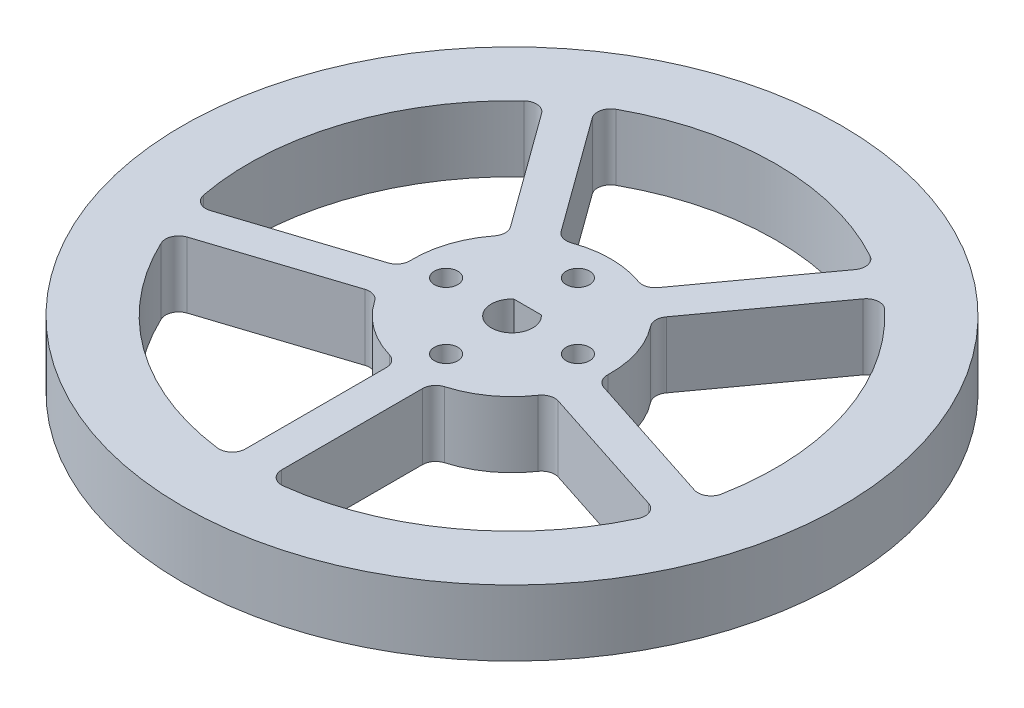
SolidWorks part; units mm, degrees
material "Nylon 6/10"
ref_plane "Front Plane" through (0, 0, 0) normal (0, 0, 1) x (1, 0, 0)
ref_plane "Top Plane" through (0, 0, 0) normal (0, 1, 0) x (1, 0, 0)
ref_plane "Right Plane" through (0, 0, 0) normal (1, 0, 0) x (0, 0, -1)
sketch "Sketch1" plane through (0, 0, 0) normal (0, 1, 0) x (1, 0, 0)
  line L0 (0, 2.8159) -> (0, -2.8159) construction
  line L2 (0, -6.7698) -> (0, -2) construction
  line L3 (-2, 0) -> (2, 0) construction
  line L4 (-1.3229, 1.5) -> (1.3229, 1.5)
  line L5 (0, 0) -> (6.7352, 6.7352) construction
  line L6 (6.7352, 6.7352) -> (6.35, 0) construction
  line L7 (6.35, 0) -> (6.7352, 6.7352) construction
  line L8 (6.7352, 6.7352) -> (0, 6.35) construction
  circle A0 centre (0, 0) radius 31.75
  arc A1 (-1.3229, 1.5) -> (1.3229, 1.5) centre (0, 0) ccw
  circle A2 centre (-6.35, 0) radius 1.1303
  circle A3 centre (0, 6.35) radius 1.1303
  circle A4 centre (6.35, 0) radius 1.1303
  circle A5 centre (0, -6.35) radius 1.1303
  dimension "D1" = 63.5
  dimension "D2" = 4
  dimension "D4" = 2.2606
  dimension "D3" = 3.5
  dimension "D5" = 6.35
  dimension "D6" = 6.35
  dimension "D7" = 6.35
  dimension "D8" = 6.35
extrude "Boss-Extrude1" add sketch "Sketch1" along normal blind 6.35
sketch "Sketch2" plane through (0, 6.35, 0) normal (0, 1, 0) x (1, 0, 0)
  circle A0 centre (0, 0) radius 9.525
  circle A1 centre (0, 0) radius 25.4
  circle A3 centre (0, 0) radius 31.75 construction
  dimension "D1" = 19.05
  dimension "D2" = 6.35
extrude "Cut-Extrude1" cut sketch "Sketch2" against normal up to surface (6.35 mm away) up to face at (6.35, 0, 1.1303)
sketch "Sketch3" plane through (0, 6.35, 0) normal (0, 1, 0) x (1, 0, 0)
  line L0 (-1.7462, -10.365) -> (-1.7462, -23.9407)
  line L1 (1.7462, -10.365) -> (1.7462, -23.9407)
  line L3 (0, -9.525) -> (0, -25.4) construction
  line L4 (-1.7462, -17.1529) -> (0, -17.4625) construction
  line L5 (0, -17.4625) -> (1.7462, -17.1529) construction
  circle A0 centre (0, 0) radius 9.525 construction
  circle A1 centre (0, 0) radius 25.4 construction
  arc A2 (-3.175, -25.2008) -> (3.175, -25.2008) centre (0, 0) ccw
  arc A3 (-2.6614, -9.1456) -> (2.6614, -9.1456) centre (0, 0) ccw
  arc A4 (-3.175, -25.2008) -> (-1.7462, -23.9407) centre (-3.0162, -23.9407) ccw
  arc A5 (1.7462, -23.9407) -> (3.175, -25.2008) centre (3.0162, -23.9407) ccw
  arc A6 (-2.6614, -9.1456) -> (-1.7462, -10.365) centre (-3.0162, -10.365) cw
  arc A7 (1.7462, -10.365) -> (2.6614, -9.1456) centre (3.0162, -10.365) cw
  dimension "D3" = 1.27
  dimension "D4" = 1.27
  dimension "D5" = 1.27
  dimension "D2" = 6.35
extrude "Boss-Extrude2" add sketch "Sketch3" against normal up to surface (6.35 mm away) contours L0 A4 A2 A5 L1 A7 A3 A6 up to face at (0, 0, 25.4)
ref_axis "Axis1" through (0, 6.35, 0) along (0, -1, 0)
pattern_circular "CirPattern1" count 5 over 360 about axis through (0, 6.35, 0) along (0, -1, 0) of "Boss-Extrude2"
ref_plane "Plane1" through (0, 3.175, 0) normal (0, 1, 0) x (1, 0, 0)
